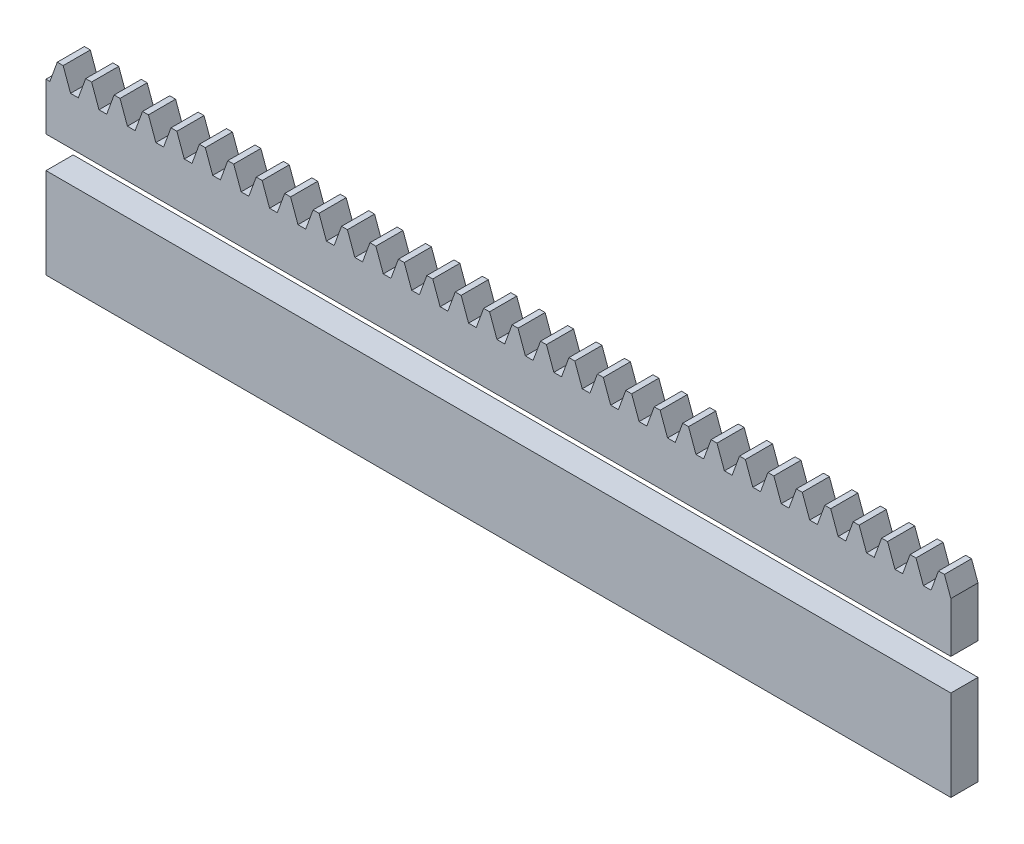
SolidWorks part; units mm, degrees
material "3.1325 (EN-AW 2017A)"
ref_plane "Płaszczyzna przednia" through (0, 0, 0) normal (0, 0, 1) x (1, 0, 0)
ref_plane "Płaszczyzna górna" through (0, 0, 0) normal (0, 1, 0) x (1, 0, 0)
ref_plane "Płaszczyzna prawa" through (0, 0, 0) normal (1, 0, 0) x (0, 0, -1)
sketch "Szkic1" plane through (0, 0, 0) normal (0, 0, 1) x (1, 0, 0)
  line L262 (400, 0) -> (400, 36.157)
  line L263 (400, 36.157) -> (397.1454, 44)
  line L264 (397.1454, 44) -> (394.536, 44)
  line L265 (394.536, 44) -> (391.2602, 35)
  line L266 (391.2602, 35) -> (387.8547, 35)
  line L267 (387.8547, 35) -> (384.579, 44)
  line L268 (384.579, 44) -> (381.9696, 44)
  line L269 (381.9696, 44) -> (378.6939, 35)
  line L270 (378.6939, 35) -> (375.2884, 35)
  line L271 (375.2884, 35) -> (372.0126, 44)
  line L272 (372.0126, 44) -> (369.4032, 44)
  line L273 (369.4032, 44) -> (366.1275, 35)
  line L274 (366.1275, 35) -> (362.722, 35)
  line L275 (362.722, 35) -> (359.4463, 44)
  line L276 (359.4463, 44) -> (356.8369, 44)
  line L277 (356.8369, 44) -> (353.5611, 35)
  line L278 (353.5611, 35) -> (350.1556, 35)
  line L279 (350.1556, 35) -> (346.8799, 44)
  line L280 (346.8799, 44) -> (344.2705, 44)
  line L281 (344.2705, 44) -> (340.9947, 35)
  line L282 (340.9947, 35) -> (337.5893, 35)
  line L283 (337.5893, 35) -> (334.3135, 44)
  line L284 (334.3135, 44) -> (331.7041, 44)
  line L285 (331.7041, 44) -> (328.4284, 35)
  line L286 (328.4284, 35) -> (325.0229, 35)
  line L287 (325.0229, 35) -> (321.7472, 44)
  line L288 (321.7472, 44) -> (319.1377, 44)
  line L289 (319.1377, 44) -> (315.862, 35)
  line L290 (315.862, 35) -> (312.4565, 35)
  line L291 (312.4565, 35) -> (309.1808, 44)
  line L292 (309.1808, 44) -> (306.5714, 44)
  line L293 (306.5714, 44) -> (303.2956, 35)
  line L294 (303.2956, 35) -> (299.8902, 35)
  line L295 (299.8902, 35) -> (296.6144, 44)
  line L296 (296.6144, 44) -> (294.005, 44)
  line L297 (294.005, 44) -> (290.7293, 35)
  line L298 (290.7293, 35) -> (287.3238, 35)
  line L299 (287.3238, 35) -> (284.0481, 44)
  line L300 (284.0481, 44) -> (281.4386, 44)
  line L301 (281.4386, 44) -> (278.1629, 35)
  line L302 (278.1629, 35) -> (274.7574, 35)
  line L303 (274.7574, 35) -> (271.4817, 44)
  line L304 (271.4817, 44) -> (268.8723, 44)
  line L305 (268.8723, 44) -> (265.5965, 35)
  line L306 (265.5965, 35) -> (262.191, 35)
  line L307 (262.191, 35) -> (258.9153, 44)
  line L308 (258.9153, 44) -> (256.3059, 44)
  line L309 (256.3059, 44) -> (253.0302, 35)
  line L310 (253.0302, 35) -> (249.6247, 35)
  line L311 (249.6247, 35) -> (246.3489, 44)
  line L312 (246.3489, 44) -> (243.7395, 44)
  line L313 (243.7395, 44) -> (240.4638, 35)
  line L314 (240.4638, 35) -> (237.0583, 35)
  line L315 (237.0583, 35) -> (233.7826, 44)
  line L316 (233.7826, 44) -> (231.1731, 44)
  line L317 (231.1731, 44) -> (227.8974, 35)
  line L318 (227.8974, 35) -> (224.4919, 35)
  line L319 (224.4919, 35) -> (221.2162, 44)
  line L320 (221.2162, 44) -> (218.6068, 44)
  line L321 (218.6068, 44) -> (215.331, 35)
  line L322 (215.331, 35) -> (211.9256, 35)
  line L323 (211.9256, 35) -> (208.6498, 44)
  line L324 (208.6498, 44) -> (206.0404, 44)
  line L325 (206.0404, 44) -> (202.7647, 35)
  line L326 (202.7647, 35) -> (199.3592, 35)
  line L327 (199.3592, 35) -> (196.0835, 44)
  line L328 (196.0835, 44) -> (193.474, 44)
  line L329 (193.474, 44) -> (190.1983, 35)
  line L330 (190.1983, 35) -> (186.7928, 35)
  line L331 (186.7928, 35) -> (183.5171, 44)
  line L332 (183.5171, 44) -> (180.9077, 44)
  line L333 (180.9077, 44) -> (177.6319, 35)
  line L334 (177.6319, 35) -> (174.2264, 35)
  line L335 (174.2264, 35) -> (170.9507, 44)
  line L336 (170.9507, 44) -> (168.3413, 44)
  line L337 (168.3413, 44) -> (165.0656, 35)
  line L338 (165.0656, 35) -> (161.6601, 35)
  line L339 (161.6601, 35) -> (158.3843, 44)
  line L340 (158.3843, 44) -> (155.7749, 44)
  line L341 (155.7749, 44) -> (152.4992, 35)
  line L342 (152.4992, 35) -> (149.0937, 35)
  line L343 (149.0937, 35) -> (145.818, 44)
  line L344 (145.818, 44) -> (143.2086, 44)
  line L345 (143.2086, 44) -> (139.9328, 35)
  line L346 (139.9328, 35) -> (136.5273, 35)
  line L347 (136.5273, 35) -> (133.2516, 44)
  line L348 (133.2516, 44) -> (130.6422, 44)
  line L349 (130.6422, 44) -> (127.3664, 35)
  line L350 (127.3664, 35) -> (123.961, 35)
  line L351 (123.961, 35) -> (120.6852, 44)
  line L352 (120.6852, 44) -> (118.0758, 44)
  line L353 (118.0758, 44) -> (114.8001, 35)
  line L354 (114.8001, 35) -> (111.3946, 35)
  line L355 (111.3946, 35) -> (108.1189, 44)
  line L356 (108.1189, 44) -> (105.5094, 44)
  line L357 (105.5094, 44) -> (102.2337, 35)
  line L358 (102.2337, 35) -> (98.8282, 35)
  line L359 (98.8282, 35) -> (95.5525, 44)
  line L360 (95.5525, 44) -> (92.9431, 44)
  line L361 (92.9431, 44) -> (89.6673, 35)
  line L362 (89.6673, 35) -> (86.2619, 35)
  line L363 (86.2619, 35) -> (82.9861, 44)
  line L364 (82.9861, 44) -> (80.3767, 44)
  line L365 (80.3767, 44) -> (77.101, 35)
  line L366 (77.101, 35) -> (73.6955, 35)
  line L367 (73.6955, 35) -> (70.4198, 44)
  line L368 (70.4198, 44) -> (67.8103, 44)
  line L369 (67.8103, 44) -> (64.5346, 35)
  line L370 (64.5346, 35) -> (61.1291, 35)
  line L371 (61.1291, 35) -> (57.8534, 44)
  line L372 (57.8534, 44) -> (55.244, 44)
  line L373 (55.244, 44) -> (51.9682, 35)
  line L374 (51.9682, 35) -> (48.5627, 35)
  line L375 (48.5627, 35) -> (45.287, 44)
  line L376 (45.287, 44) -> (42.6776, 44)
  line L377 (42.6776, 44) -> (39.4019, 35)
  line L378 (39.4019, 35) -> (35.9964, 35)
  line L379 (35.9964, 35) -> (32.7206, 44)
  line L380 (32.7206, 44) -> (30.1112, 44)
  line L381 (30.1112, 44) -> (26.8355, 35)
  line L382 (26.8355, 35) -> (23.43, 35)
  line L383 (23.43, 35) -> (20.1543, 44)
  line L384 (20.1543, 44) -> (17.5448, 44)
  line L385 (17.5448, 44) -> (14.2691, 35)
  line L386 (14.2691, 35) -> (10.8636, 35)
  line L387 (10.8636, 35) -> (7.5879, 44)
  line L388 (7.5879, 44) -> (4.9785, 44)
  line L389 (4.9785, 44) -> (1.7027, 35)
  line L390 (1.7027, 35) -> (0, 35)
  line L391 (0, 35) -> (0, 0)
  line L392 (0, 0) -> (400, 0)
extrude "Dodanie-wyciągnięcie1" add sketch "Szkic1" along normal blind 12
sketch "Szkic3" plane through (0, 0, 12) normal (0, 0, 1) x (1, 0, 0)
  line L0 (400, 0) -> (400, 36.157) construction
  line L1 (0, 0) -> (400, 0)
  line L2 (0, 0) -> (0, 14)
  line L3 (0, 14) -> (400, 14)
  line L4 (400, 0) -> (400, 14)
  line L5 (200, 14) -> (200, 0) construction
  line L6 (0, 7) -> (400, 7) construction
  point P136 (200, 7)
  dimension "D1" = 14
extrude "Wytnij-wyciągnięcie1" cut sketch "Szkic3" against normal up to next
sketch "Szkic2" plane through (0, 0, 0) normal (0, -1, 0) x (1, 0, 0)
  line L4 (0, 0) -> (400, 0)
  line L5 (400, 0) -> (400, 12)
  line L6 (400, 12) -> (0, 12)
  line L7 (0, 12) -> (0, 0)
  line L8 (0, 0) -> (400, 0)
  line L9 (400, 0) -> (400, 12)
  line L10 (400, 12) -> (0, 12)
  line L11 (0, 12) -> (0, 0)
  dimension "D1" = 0
extrude "Dodanie-wyciągnięcie2" add sketch "Szkic2" along normal blind 40
